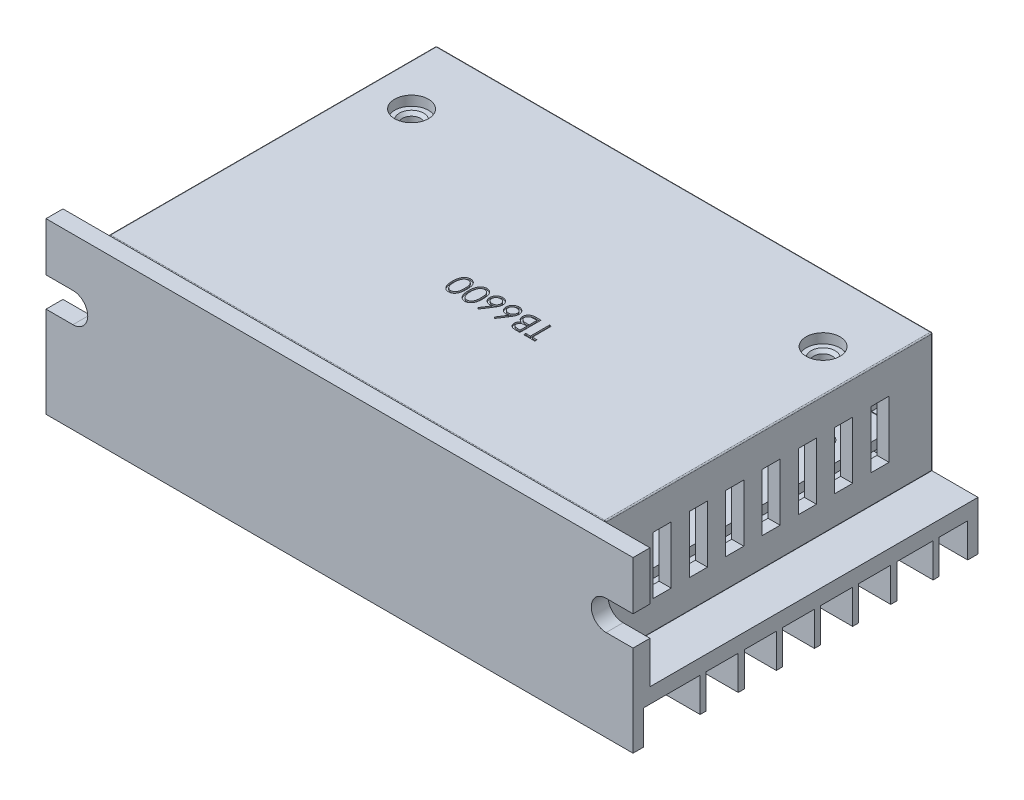
SolidWorks part; units mm, degrees
ref_plane "Front Plane" through (0, 0, 0) normal (0, 0, 1) x (1, 0, 0)
ref_plane "Top Plane" through (0, 0, 0) normal (0, 1, 0) x (1, 0, 0)
ref_plane "Right Plane" through (0, 0, 0) normal (1, 0, 0) x (0, 0, -1)
sketch "Sketch1" plane through (0, 0, 0) normal (1, 0, 0) x (0, 0, -1)
  line L1 (-28.5, 14) -> (28.5, 14)
  line L2 (-28.5, 14) -> (-28.5, -14)
  line L3 (-28.5, -14) -> (28.5, -14)
  line L4 (28.5, 14) -> (28.5, -14)
  line L5 (-28.5, 14) -> (28.5, -14) construction
  line L6 (-28.5, -14) -> (28.5, 14) construction
  point P0 (0, 0)
  dimension "D1" = 28
  dimension "D2" = 57
extrude "Base and Heat Sink" add sketch "Sketch1" along normal mid plane 97
sketch "Sketch2" plane through (0, 0, 0) normal (1, 0, 0) x (0, 0, -1)
  line L0 (28.5, 14) -> (-28.5, 14) construction
  line L1 (-25.7, 14) -> (28.5, 14)
  line L2 (-25.7, 14) -> (-25.7, -5.88)
  line L3 (-25.7, -5.88) -> (28.5, -5.88)
  line L4 (28.5, 14) -> (28.5, -5.88)
  line L5 (28.5, -14) -> (28.5, 14) construction
  line L6 (-28.5, 14) -> (-28.5, -14) construction
  line L7 (-28.5, -14) -> (28.5, -14) construction
  dimension "D1" = 2.8
  dimension "D2" = 8.12
extrude "Cut-Extrude1" cut sketch "Sketch2" against normal through all both and the other way through all
sketch "Sketch3" plane through (0, 0, 0) normal (1, 0, 0) x (0, 0, -1)
  line L0 (-28.5, -14) -> (28.5, -14) construction
  line L1 (-26.8, -14) -> (-17.42, -14)
  line L2 (-26.8, -14) -> (-26.8, -8.38)
  line L3 (-26.8, -8.38) -> (-17.42, -8.38)
  line L4 (-17.42, -14) -> (-17.42, -8.38)
  line L5 (-28.5, 14) -> (-28.5, -14) construction
  line L6 (-25.7, -5.88) -> (28.5, -5.88) construction
  line L7 (-10.12, -14) -> (-10.12, -8.38)
  line L8 (-16.42, -14) -> (-11.12, -14)
  line L9 (-16.42, -14) -> (-16.42, -8.38)
  line L10 (-16.42, -8.38) -> (-11.12, -8.38)
  line L11 (-11.12, -14) -> (-11.12, -8.38)
  line L12 (-10.12, -14) -> (-4.82, -14)
  line L13 (-4.82, -14) -> (-4.82, -8.38)
  line L14 (-3.82, -14) -> (-3.82, -8.38)
  line L15 (-3.82, -14) -> (1.48, -14)
  line L16 (1.48, -14) -> (1.48, -8.38)
  line L17 (2.48, -14) -> (2.48, -8.38)
  line L18 (2.48, -14) -> (7.78, -14)
  line L19 (7.78, -14) -> (7.78, -8.38)
  line L20 (8.78, -14) -> (8.78, -8.38)
  line L21 (8.78, -14) -> (14.08, -14)
  line L22 (14.08, -14) -> (14.08, -8.38)
  line L23 (28.5, -14) -> (28.5, -5.88) construction
  line L24 (15.08, -14) -> (21.08, -14)
  line L25 (15.08, -14) -> (15.08, -8.38)
  line L26 (15.08, -8.38) -> (21.08, -8.38)
  line L27 (21.08, -14) -> (21.08, -8.38)
  line L28 (22.08, -14) -> (26.8, -14)
  line L29 (22.08, -14) -> (22.08, -8.38)
  line L30 (22.08, -8.38) -> (26.8, -8.38)
  line L31 (26.8, -14) -> (26.8, -8.38)
  line L32 (-10.12, -8.38) -> (-4.82, -8.38)
  line L33 (-3.82, -8.38) -> (1.48, -8.38)
  line L34 (2.48, -8.38) -> (7.78, -8.38)
  line L35 (8.78, -8.38) -> (14.08, -8.38)
  dimension "D1" = 1.7
  dimension "D2" = 9.38
  dimension "D3" = 2.5
  dimension "D4" = 1
  dimension "D5" = 5.3
  dimension "D7" = 1
  dimension "D8" = 1
  dimension "D9" = 1
  dimension "D10" = 6
  dimension "D11" = 1
  dimension "D12" = 1.7
  dimension "D6" = 5
extrude "Cut-Extrude2" cut sketch "Sketch3" against normal through all both and the other way through all
sketch "Sketch4" plane through (0, -5.88, 0) normal (0, 1, 0) x (1, 0, 0)
  line L2 (-34, -20.8) -> (34, -20.8) construction
  line L3 (-34, -20.8) -> (-34, 17.4) construction
  line L4 (-34, 17.4) -> (34, 17.4) construction
  line L5 (34, -20.8) -> (34, 17.4) construction
  line L6 (-34, -20.8) -> (34, 17.4) construction
  line L7 (-34, 17.4) -> (34, -20.8) construction
  line L8 (-48.5, 28.5) -> (48.5, 28.5) construction
  circle A0 centre (-34, 17.4) radius 1.5
  circle A1 centre (34, 17.4) radius 1.5
  circle A2 centre (34, -20.8) radius 1.5
  circle A3 centre (-34, -20.8) radius 1.5
  point P0 (0, -1.7)
  dimension "D4" = 3
  dimension "D1" = 68
  dimension "D2" = 11.1
  dimension "D3" = 38.2
extrude "Cut-Extrude3" cut sketch "Sketch4" against normal blind 3
sketch "Sketch5" plane through (0, 0, 28.5) normal (0, 0, 1) x (1, 0, 0)
  line L0 (-48.5, 3.5) -> (52.8108, 3.5) construction
  line L1 (-48.5, 14) -> (-48.5, -14) construction
  line L2 (48.5, 14) -> (-48.5, 14) construction
  line L3 (48.5, 14) -> (48.5, -14) construction
  line L4 (41.6, 6.1377) -> (41.6, 0) construction
  line L5 (44.05, 1.05) -> (48.5, 1.05)
  line L6 (44.05, 5.95) -> (48.5, 5.95)
  line L7 (-41.6, 1.05) -> (-41.6, 6.49) construction
  line L8 (-44.05, 5.95) -> (-48.5, 5.95)
  line L9 (-44.05, 1.05) -> (-48.5, 1.05)
  line L10 (-48.5, 1.05) -> (-48.5, 5.95)
  line L11 (48.5, 1.05) -> (48.5, 5.95)
  arc A0 (44.05, 5.95) -> (44.05, 1.05) centre (44.05, 3.5) ccw
  arc A1 (-44.05, 1.05) -> (-44.05, 5.95) centre (-44.05, 3.5) ccw
  dimension "D2" = 4.9
  dimension "D4" = 6.9
  dimension "D1" = 10.5
  dimension "D3" = 4.45
extrude "Cut-Extrude4" cut sketch "Sketch5" against normal blind 3
sketch "Sketch6" plane through (0, 0, 0) normal (1, 0, 0) x (0, 0, -1)
  line L0 (-25.7, 14) -> (-25.7, 5.95) construction
  line L1 (-25.7, 14) -> (28.5, 14)
  line L2 (-25.7, 14) -> (-25.7, -5.88)
  line L3 (-25.7, -5.88) -> (28.5, -5.88)
  line L4 (28.5, 14) -> (28.5, -5.88)
  line L5 (-25.7, 14) -> (-28.5, 14) construction
extrude "Plastic Casing" add sketch "Sketch6" along normal mid plane 82 separate body
shell "Shell1" thickness 2 removed face at (0, 4.06, 25.7) removed face at (0, -5.88, -1.4)
fillet "Fillet1" radius 0.2 11 edges at (-41, -5.88, -1.4) (-41, 4.06, 25.7) (0, 14, 25.7) (-41, 14, -1.4) (0, -5.88, -28.5) (0, 14, -28.5) (-41, 4.06, -28.5) (41, 14, -1.4) (41, 4.06, -28.5) (41, -5.88, -1.4) (41, 4.06, 25.7)
sketch "Sketch9" plane through (0, 14, 0) normal (0, 1, 0) x (1, 0, 0)
  circle A0 centre (-34, 17.4) radius 1.5 construction
  circle A1 centre (34, 17.4) radius 1.5 construction
  circle A2 centre (-34, 17.4) radius 1.5
  circle A3 centre (34, 17.4) radius 1.5
sketch "Sketch10" plane through (0, 12, 0) normal (0, -1, 0) x (1, 0, 0)
  circle A0 centre (34, -17.4) radius 3.975
  circle A1 centre (-34, -17.4) radius 3.975
  dimension "D1" = 7.95
extrude "Boss-Extrude3" add sketch "Sketch10" along normal blind 1.2
sketch "Sketch11" plane through (0, 10.8, 0) normal (0, -1, 0) x (1, 0, 0)
  circle A0 centre (-34, -17.4) radius 1.5 construction
  circle A1 centre (34, -17.4) radius 1.5 construction
  circle A2 centre (-34, -17.4) radius 1.5
  circle A3 centre (34, -17.4) radius 1.5
extrude "Cut-Extrude5" cut sketch "Sketch11" against normal blind 11.2
sketch "Sketch12" plane through (0, 14, 0) normal (0, 1, 0) x (1, 0, 0)
  circle A0 centre (-34, 17.4) radius 2.8
  circle A1 centre (34, 17.4) radius 2.8
  dimension "D1" = 5.6
extrude "Cut-Extrude6" cut sketch "Sketch12" against normal blind 1.6
chamfer "Chamfer1" distance 0.5 angle 45 2 edges at (34, 12.4, -15.9) (-34, 12.4, -15.9)
sketch "Sketch13" plane through (0, 0, -28.5) normal (0, 0, -1) x (-1, 0, 0)
  line L0 (41, 13.8) -> (41, -5.68) construction
  line L1 (-33.9, -0.38) -> (32.5, -0.38)
  line L2 (-33.9, -0.38) -> (-33.9, 10.25)
  line L3 (-33.9, 10.25) -> (32.5, 10.25)
  line L4 (32.5, -0.38) -> (32.5, 10.25)
  line L5 (-41, -5.68) -> (-41, 13.8) construction
  line L6 (-40.8, 14) -> (40.8, 14) construction
  line L7 (40.8, -5.88) -> (-40.8, -5.88) construction
  dimension "D1" = 8.5
  dimension "D2" = 7.1
  dimension "D3" = 3.75
  dimension "D4" = 5.5
extrude "Cut-Extrude7" cut sketch "Sketch13" against normal up to surface (2 mm away) up to face at (0, 3.06, -26.5)
sketch "Sketch14" plane through (0, 0, 0) normal (1, 0, 0) x (0, 0, -1)
  line L0 (28.5, -5.68) -> (28.5, 13.8) construction
  line L1 (21.3, 8.45) -> (18.3, 8.45)
  line L2 (21.3, 8.45) -> (21.3, -1.0244)
  line L3 (21.3, -1.0244) -> (18.3, -1.0244)
  line L4 (18.3, 8.45) -> (18.3, -1.0244)
  line L5 (28.3, 14) -> (-25.5, 14) construction
  line L7 (15.3, 8.45) -> (12.3, 8.45)
  line L8 (15.3, 8.45) -> (15.3, -1.0244)
  line L9 (15.3, -1.0244) -> (12.3, -1.0244)
  line L10 (12.3, 8.45) -> (12.3, -1.0244)
  line L11 (9.3, 8.45) -> (6.3, 8.45)
  line L12 (9.3, 8.45) -> (9.3, -1.0244)
  line L13 (9.3, -1.0244) -> (6.3, -1.0244)
  line L14 (6.3, 8.45) -> (6.3, -1.0244)
  line L15 (3.3, 8.45) -> (0.3, 8.45)
  line L16 (3.3, 8.45) -> (3.3, -1.0244)
  line L17 (3.3, -1.0244) -> (0.3, -1.0244)
  line L18 (0.3, 8.45) -> (0.3, -1.0244)
  line L19 (-2.7, 8.45) -> (-5.7, 8.45)
  line L20 (-2.7, 8.45) -> (-2.7, -1.0244)
  line L21 (-2.7, -1.0244) -> (-5.7, -1.0244)
  line L22 (-5.7, 8.45) -> (-5.7, -1.0244)
  line L23 (-8.7, 8.45) -> (-11.7, 8.45)
  line L24 (-8.7, 8.45) -> (-8.7, -1.0244)
  line L25 (-8.7, -1.0244) -> (-11.7, -1.0244)
  line L26 (-11.7, 8.45) -> (-11.7, -1.0244)
  line L27 (-14.7, 8.45) -> (-17.7, 8.45)
  line L28 (-14.7, 8.45) -> (-14.7, -1.0244)
  line L29 (-14.7, -1.0244) -> (-17.7, -1.0244)
  line L30 (-17.7, 8.45) -> (-17.7, -1.0244)
  dimension "D1" = 7.2
  dimension "D2" = 3
  dimension "D3" = 5.55
  dimension "D4" = 7
extrude "Cut-Extrude9" cut sketch "Sketch14" along normal up to surface (41 mm away) up to face at (41, 4.06, -1.4)
sketch "Sketch15" plane through (-41, 0, 0) normal (-1, 0, 0) x (0, 0, 1)
  line L0 (14.7, 8.45) -> (14.7, -1.0244) construction
  line L1 (17.7, 8.45) -> (14.7, 8.45) construction
  line L2 (17.7, -1.0244) -> (17.7, 8.45) construction
  line L3 (14.7, -1.0244) -> (17.7, -1.0244) construction
  line L4 (8.7, -1.0244) -> (11.7, -1.0244) construction
  line L5 (8.7, 8.45) -> (8.7, -1.0244) construction
  line L6 (11.7, 8.45) -> (8.7, 8.45) construction
  line L7 (11.7, -1.0244) -> (11.7, 8.45) construction
  line L8 (-21.3, -1.0244) -> (-18.3, -1.0244) construction
  line L9 (-21.3, 8.45) -> (-21.3, -1.0244) construction
  line L10 (-18.3, 8.45) -> (-21.3, 8.45) construction
  line L11 (-18.3, -1.0244) -> (-18.3, 8.45) construction
  line L12 (14.7, 8.45) -> (14.7, -1.0244)
  line L13 (17.7, 8.45) -> (14.7, 8.45)
  line L14 (17.7, -1.0244) -> (17.7, 8.45)
  line L15 (14.7, -1.0244) -> (17.7, -1.0244)
  line L16 (8.7, -1.0244) -> (11.7, -1.0244)
  line L17 (8.7, 8.45) -> (8.7, -1.0244)
  line L18 (11.7, 8.45) -> (8.7, 8.45)
  line L19 (11.7, -1.0244) -> (11.7, 8.45)
  line L20 (-21.3, -1.0244) -> (-18.3, -1.0244)
  line L21 (-21.3, 8.45) -> (-21.3, -1.0244)
  line L22 (-18.3, 8.45) -> (-21.3, 8.45)
  line L23 (-18.3, -1.0244) -> (-18.3, 8.45)
extrude "Cut-Extrude10" cut sketch "Sketch15" against normal up to surface (2 mm away) up to face at (-39, 3.06, -0.4)
sketch "Sketch16" plane through (-41, 0, 0) normal (-1, 0, 0) x (0, 0, 1)
  line L0 (25.7, -5.88) -> (-28.3, -5.88) construction
  line L1 (-15.1674, 10.82) -> (3.6826, 10.82)
  line L2 (-15.1674, 10.82) -> (-15.1674, 0.62)
  line L3 (-15.1674, 0.62) -> (3.6826, 0.62)
  line L4 (3.6826, 10.82) -> (3.6826, 0.62)
  dimension "D1" = 18.85
  dimension "D2" = 10.2
  dimension "D3" = 6.5
extrude "Cut-Extrude11" cut sketch "Sketch16" against normal up to surface (2 mm away) up to face at (-39, 3.7128, 10.2)
ref_plane "Plane1" through (0, -0.88, 0) normal (0, 1, 0) x (1, 0, 0)
sketch "Sketch17" plane through (0, -0.88, 0) normal (0, 1, 0) x (1, 0, 0)
  line L0 (-48.5, -25.7) -> (48.5, -25.7) construction
  line L1 (38.275, -24.7) -> (-38.275, -24.7)
  line L2 (38.275, -24.7) -> (38.275, 25.4)
  line L3 (38.275, 25.4) -> (-38.275, 25.4)
  line L4 (-38.275, -24.7) -> (-38.275, 25.4)
  circle A0 centre (-34, -20.8) radius 1.5 construction
  circle A1 centre (-34, 17.4) radius 1.5 construction
  circle A2 centre (34, 17.4) radius 1.5 construction
  circle A3 centre (34, -20.8) radius 1.5 construction
  circle A4 centre (-34, -20.8) radius 1.5
  circle A5 centre (-34, 17.4) radius 1.5
  circle A6 centre (34, 17.4) radius 1.5
  circle A7 centre (34, -20.8) radius 1.5
  point P18 (0, -24.7)
  dimension "D1" = 50.1
  dimension "D2" = 1
  dimension "D3" = 76.55
extrude "Boss-Extrude4" add sketch "Sketch17" along normal blind 1.5 separate body
ref_plane "Plane2" through (0, 0, -33.5) normal (0, 0, -1) x (-1, 0, 0)
sketch "Sketch18" plane through (0, 0, -33.5) normal (0, 0, -1) x (-1, 0, 0)
  line L0 (-38.275, 0.62) -> (38.275, 0.62) construction
  line L1 (-33.9, 0.62) -> (27.4, 0.62)
  line L2 (-33.9, 0.62) -> (-33.9, 8.62)
  line L3 (-33.9, 8.62) -> (27.4, 8.62)
  line L4 (27.4, 0.62) -> (27.4, 8.62)
  line L5 (-33.9, 10.25) -> (-33.9, -0.38) construction
  dimension "D1" = 8
  dimension "D2" = 61.3
extrude "Connector" add sketch "Sketch18" against normal blind 12 separate body
sketch "Sketch19" plane through (0, 0, -33.5) normal (0, 0, -1) x (-1, 0, 0)
  line L0 (-3.3029, 9.6458) -> (-3.3029, -7.8401) construction
  line L1 (-33.9, 7.1295) -> (-33.9, 1.6983) construction
  line L2 (-33.9, 8.62) -> (-33.9, 0.62) construction
  line L3 (-28.7917, 7.1867) -> (-28.7917, 1.7555) construction
  line L4 (-23.6833, 7.2439) -> (-23.6833, 1.8127) construction
  line L5 (-18.575, 7.3012) -> (-18.575, 1.8699) construction
  line L6 (-13.4667, 7.3584) -> (-13.4667, 1.9272) construction
  line L7 (-8.3583, 7.4156) -> (-8.3583, 1.9844) construction
  line L8 (-3.25, 7.4728) -> (-3.25, 2.0416) construction
  line L9 (1.8583, 7.53) -> (1.8583, 2.0988) construction
  line L10 (6.9667, 7.5873) -> (6.9667, 2.1561) construction
  line L11 (12.075, 7.6445) -> (12.075, 2.2133) construction
  line L12 (17.1833, 7.7017) -> (17.1833, 2.2705) construction
  line L13 (22.2917, 7.7589) -> (22.2917, 2.3277) construction
  line L14 (27.4, 7.8162) -> (27.4, 2.385) construction
  line L15 (-33.9, 7.1295) -> (-28.7917, 7.1867) construction
  dimension "D2" = 5.1087
  dimension "D1" = 13
sketch "Sketch20" plane through (0, 0, -33.5) normal (0, 0, -1) x (-1, 0, 0)
  line L0 (-33.9, 8.62) -> (-33.9, 0.62) construction
  line L1 (-33.9, 7.02) -> (27.4, 7.02)
  line L2 (-33.9, 7.02) -> (-33.9, 1.62)
  line L3 (-33.9, 1.62) -> (-33.3515, 1.62)
  line L4 (27.4, 7.02) -> (27.4, 1.62)
  line L5 (27.4, 0.62) -> (27.4, 8.62) construction
  line L6 (27.4, 8.62) -> (-33.9, 8.62) construction
  line L7 (-31.3458, 16.2754) -> (-31.3458, 1.62) construction
  line L8 (-28.7917, 7.1867) -> (-28.7917, 1.7555) construction
  line L9 (-29.3401, 1.62) -> (-28.2394, 1.62)
  line L10 (24.8458, 7.7121) -> (24.8458, 1.62) construction
  line L11 (22.2917, 7.7589) -> (22.2917, 2.3277) construction
  line L12 (-33.3515, 1.62) -> (-28.2402, 1.6208) construction
  line L13 (-24.2297, 1.62) -> (-23.1272, 1.62)
  line L14 (-19.1193, 1.62) -> (-18.0151, 1.62)
  line L15 (-14.0089, 1.62) -> (-12.9029, 1.62)
  line L16 (-8.8985, 1.62) -> (-7.7907, 1.62)
  line L17 (-3.7881, 1.62) -> (-2.6786, 1.62)
  line L18 (1.3223, 1.62) -> (2.4336, 1.62)
  line L19 (6.4327, 1.62) -> (7.5458, 1.62)
  line L20 (11.5432, 1.62) -> (12.6579, 1.62)
  line L21 (16.6536, 1.62) -> (17.7701, 1.62)
  line L22 (21.764, 1.62) -> (22.8823, 1.62)
  line L23 (26.8744, 1.62) -> (27.4, 1.62)
  arc A0 (-33.3515, 1.62) -> (-29.3401, 1.62) centre (-31.3458, 3.7715) ccw
  arc A1 (-28.2394, 1.62) -> (-24.2297, 1.62) centre (-26.2345, 3.7723) ccw
  arc A2 (-23.1272, 1.62) -> (-19.1193, 1.62) centre (-21.1233, 3.7731) ccw
  arc A3 (-18.0151, 1.62) -> (-14.0089, 1.62) centre (-16.012, 3.7739) ccw
  arc A4 (-12.9029, 1.62) -> (-8.8985, 1.62) centre (-10.9007, 3.7748) ccw
  arc A5 (-7.7907, 1.62) -> (-3.7881, 1.62) centre (-5.7894, 3.7756) ccw
  arc A6 (-2.6786, 1.62) -> (1.3223, 1.62) centre (-0.6781, 3.7764) ccw
  arc A7 (2.4336, 1.62) -> (6.4327, 1.62) centre (4.4332, 3.7772) ccw
  arc A8 (7.5458, 1.62) -> (11.5432, 1.62) centre (9.5445, 3.778) ccw
  arc A9 (12.6579, 1.62) -> (16.6536, 1.62) centre (14.6557, 3.7788) ccw
  arc A10 (17.7701, 1.62) -> (21.764, 1.62) centre (19.767, 3.7796) ccw
  arc A11 (22.8823, 1.62) -> (26.8744, 1.62) centre (24.8783, 3.7804) ccw
  dimension "D5" = 2.9414
  dimension "D1" = 5.4
  dimension "D2" = 1.6
  dimension "D4" = 5.1113
  dimension "D3" = 12
extrude "Cut-Extrude12" cut sketch "Sketch20" against normal blind 10.5
sketch "Sketch21" plane through (0, 0, -23) normal (0, 0, -1) x (-1, 0, 0)
  line L0 (-31.3458, 6.0298) -> (-31.3458, 2.1596) construction
  line L1 (-33.9, 7.1295) -> (-33.9, 1.6983) construction
  line L2 (-28.7917, 7.1867) -> (-28.7917, 1.7555) construction
  line L3 (-31.3458, 4.0947) -> (24.8458, 4.0947) construction
  line L4 (24.8458, 6.0298) -> (24.8458, 2.1596) construction
  line L5 (22.2917, 7.7589) -> (22.2917, 2.3277) construction
  line L6 (27.4, 7.8162) -> (27.4, 2.385) construction
  line L7 (-26.4875, 4.3447) -> (-25.9875, 4.3447)
  line L8 (-31.5958, 4.3447) -> (-31.0958, 4.3447)
  line L9 (-31.5958, 4.3447) -> (-31.5958, 3.8447)
  line L10 (-31.5958, 3.8447) -> (-31.0958, 3.8447)
  line L11 (-31.0958, 4.3447) -> (-31.0958, 3.8447)
  line L12 (-31.5958, 4.3447) -> (-31.0958, 3.8447) construction
  line L13 (-31.5958, 3.8447) -> (-31.0958, 4.3447) construction
  line L14 (-26.4875, 4.3447) -> (-26.4875, 3.8447)
  line L15 (-26.4875, 3.8447) -> (-25.9875, 3.8447)
  line L16 (-25.9875, 4.3447) -> (-25.9875, 3.8447)
  line L17 (-26.4875, 4.3447) -> (-25.9875, 3.8447) construction
  line L18 (-26.4875, 3.8447) -> (-25.9875, 4.3447) construction
  line L19 (-21.3792, 4.3447) -> (-20.8792, 4.3447)
  line L20 (-21.3792, 4.3447) -> (-21.3792, 3.8447)
  line L21 (-21.3792, 3.8447) -> (-20.8792, 3.8447)
  line L22 (-20.8792, 4.3447) -> (-20.8792, 3.8447)
  line L23 (-21.3792, 4.3447) -> (-20.8792, 3.8447) construction
  line L24 (-21.3792, 3.8447) -> (-20.8792, 4.3447) construction
  line L25 (-16.2708, 4.3447) -> (-15.7708, 4.3447)
  line L26 (-16.2708, 4.3447) -> (-16.2708, 3.8447)
  line L27 (-16.2708, 3.8447) -> (-15.7708, 3.8447)
  line L28 (-15.7708, 4.3447) -> (-15.7708, 3.8447)
  line L29 (-16.2708, 4.3447) -> (-15.7708, 3.8447) construction
  line L30 (-16.2708, 3.8447) -> (-15.7708, 4.3447) construction
  line L31 (-11.1625, 4.3447) -> (-10.6625, 4.3447)
  line L32 (-11.1625, 4.3447) -> (-11.1625, 3.8447)
  line L33 (-11.1625, 3.8447) -> (-10.6625, 3.8447)
  line L34 (-10.6625, 4.3447) -> (-10.6625, 3.8447)
  line L35 (-11.1625, 4.3447) -> (-10.6625, 3.8447) construction
  line L36 (-11.1625, 3.8447) -> (-10.6625, 4.3447) construction
  line L37 (-6.0542, 4.3447) -> (-5.5542, 4.3447)
  line L38 (-6.0542, 4.3447) -> (-6.0542, 3.8447)
  line L39 (-6.0542, 3.8447) -> (-5.5542, 3.8447)
  line L40 (-5.5542, 4.3447) -> (-5.5542, 3.8447)
  line L41 (-6.0542, 4.3447) -> (-5.5542, 3.8447) construction
  line L42 (-6.0542, 3.8447) -> (-5.5542, 4.3447) construction
  line L43 (-0.9458, 4.3447) -> (-0.4458, 4.3447)
  line L44 (-0.9458, 4.3447) -> (-0.9458, 3.8447)
  line L45 (-0.9458, 3.8447) -> (-0.4458, 3.8447)
  line L46 (-0.4458, 4.3447) -> (-0.4458, 3.8447)
  line L47 (-0.9458, 4.3447) -> (-0.4458, 3.8447) construction
  line L48 (-0.9458, 3.8447) -> (-0.4458, 4.3447) construction
  line L49 (4.1625, 4.3447) -> (4.6625, 4.3447)
  line L50 (4.1625, 4.3447) -> (4.1625, 3.8447)
  line L51 (4.1625, 3.8447) -> (4.6625, 3.8447)
  line L52 (4.6625, 4.3447) -> (4.6625, 3.8447)
  line L53 (4.1625, 4.3447) -> (4.6625, 3.8447) construction
  line L54 (4.1625, 3.8447) -> (4.6625, 4.3447) construction
  line L55 (9.2708, 4.3447) -> (9.7708, 4.3447)
  line L56 (9.2708, 4.3447) -> (9.2708, 3.8447)
  line L57 (9.2708, 3.8447) -> (9.7708, 3.8447)
  line L58 (9.7708, 4.3447) -> (9.7708, 3.8447)
  line L59 (9.2708, 4.3447) -> (9.7708, 3.8447) construction
  line L60 (9.2708, 3.8447) -> (9.7708, 4.3447) construction
  line L61 (14.3792, 4.3447) -> (14.8792, 4.3447)
  line L62 (14.3792, 4.3447) -> (14.3792, 3.8447)
  line L63 (14.3792, 3.8447) -> (14.8792, 3.8447)
  line L64 (14.8792, 4.3447) -> (14.8792, 3.8447)
  line L65 (14.3792, 4.3447) -> (14.8792, 3.8447) construction
  line L66 (14.3792, 3.8447) -> (14.8792, 4.3447) construction
  line L67 (19.4875, 4.3447) -> (19.9875, 4.3447)
  line L68 (19.4875, 4.3447) -> (19.4875, 3.8447)
  line L69 (19.4875, 3.8447) -> (19.9875, 3.8447)
  line L70 (19.9875, 4.3447) -> (19.9875, 3.8447)
  line L71 (19.4875, 4.3447) -> (19.9875, 3.8447) construction
  line L72 (19.4875, 3.8447) -> (19.9875, 4.3447) construction
  line L73 (24.5958, 4.3447) -> (25.0958, 4.3447)
  line L74 (24.5958, 4.3447) -> (24.5958, 3.8447)
  line L75 (24.5958, 3.8447) -> (25.0958, 3.8447)
  line L76 (25.0958, 4.3447) -> (25.0958, 3.8447)
  line L77 (24.5958, 4.3447) -> (25.0958, 3.8447) construction
  line L78 (24.5958, 3.8447) -> (25.0958, 4.3447) construction
  line L79 (-31.5958, 4.3447) -> (-26.4875, 4.3447) construction
  dimension "D1" = 0.5
  dimension "D2" = 0.5
  dimension "D4" = 5.1083
  dimension "D3" = 12
extrude "Boss-Extrude6" add sketch "Sketch21" along normal blind 10.5
chamfer "Chamfer2" distance 0.6 angle 15 48 edges at (-24.8458, 3.8447, -33.5) (-24.5958, 4.0947, -33.5) (-24.8458, 4.3447, -33.5) (-25.0958, 4.0947, -33.5) (-19.7375, 3.8447, -33.5) (-19.4875, 4.0947, -33.5) (-19.7375, 4.3447, -33.5) (-19.9875, 4.0947, -33.5) (-14.6292, 3.8447, -33.5) (-14.3792, 4.0947, -33.5) (-14.6292, 4.3447, -33.5) (-14.8792, 4.0947, -33.5) (-9.5208, 3.8447, -33.5) (-9.2708, 4.0947, -33.5) (-9.5208, 4.3447, -33.5) (-9.7708, 4.0947, -33.5) (-4.4125, 3.8447, -33.5) (-4.1625, 4.0947, -33.5) (-4.4125, 4.3447, -33.5) (-4.6625, 4.0947, -33.5) (0.6958, 3.8447, -33.5) (0.9458, 4.0947, -33.5) (0.6958, 4.3447, -33.5) (0.4458, 4.0947, -33.5) (5.8042, 3.8447, -33.5) (6.0542, 4.0947, -33.5) (5.8042, 4.3447, -33.5) (5.5542, 4.0947, -33.5) (10.9125, 3.8447, -33.5) (11.1625, 4.0947, -33.5) (10.9125, 4.3447, -33.5) (10.6625, 4.0947, -33.5) (16.0208, 3.8447, -33.5) (16.2708, 4.0947, -33.5) (16.0208, 4.3447, -33.5) (15.7708, 4.0947, -33.5) (21.1292, 3.8447, -33.5) (21.3792, 4.0947, -33.5) (21.1292, 4.3447, -33.5) (20.8792, 4.0947, -33.5) (26.2375, 3.8447, -33.5) (26.4875, 4.0947, -33.5) (26.2375, 4.3447, -33.5) (25.9875, 4.0947, -33.5) (31.3458, 3.8447, -33.5) (31.5958, 4.0947, -33.5) (31.3458, 4.3447, -33.5) (31.0958, 4.0947, -33.5) first distance on face at (-24.8458, 3.8447, -28.25) first distance on face at (-24.5958, 4.0947, -28.25) first distance on face at (-24.8458, 4.3447, -28.25) first distance on face at (-25.0958, 4.0947, -28.25) first distance on face at (-19.7375, 3.8447, -28.25) first distance on face at (-19.4875, 4.0947, -28.25) first distance on face at (-19.7375, 4.3447, -28.25) first distance on face at (-19.9875, 4.0947, -28.25) first distance on face at (-14.6292, 3.8447, -28.25) first distance on face at (-14.3792, 4.0947, -28.25) first distance on face at (-14.6292, 4.3447, -28.25) first distance on face at (-14.8792, 4.0947, -28.25) first distance on face at (-9.5208, 3.8447, -28.25) first distance on face at (-9.2708, 4.0947, -28.25) first distance on face at (-9.5208, 4.3447, -28.25) first distance on face at (-9.7708, 4.0947, -28.25) first distance on face at (-4.4125, 3.8447, -28.25) first distance on face at (-4.1625, 4.0947, -28.25) first distance on face at (-4.4125, 4.3447, -28.25) first distance on face at (-4.6625, 4.0947, -28.25) first distance on face at (0.6958, 3.8447, -28.25) first distance on face at (0.9458, 4.0947, -28.25) first distance on face at (0.6958, 4.3447, -28.25) first distance on face at (0.4458, 4.0947, -28.25) first distance on face at (5.8042, 3.8447, -28.25) first distance on face at (6.0542, 4.0947, -28.25) first distance on face at (5.8042, 4.3447, -28.25) first distance on face at (5.5542, 4.0947, -28.25) first distance on face at (10.9125, 3.8447, -28.25) first distance on face at (11.1625, 4.0947, -28.25) first distance on face at (10.9125, 4.3447, -28.25) first distance on face at (10.6625, 4.0947, -28.25) first distance on face at (16.0208, 3.8447, -28.25) first distance on face at (16.2708, 4.0947, -28.25) first distance on face at (16.0208, 4.3447, -28.25) first distance on face at (15.7708, 4.0947, -28.25) first distance on face at (21.1292, 3.8447, -28.25) first distance on face at (21.3792, 4.0947, -28.25) first distance on face at (21.1292, 4.3447, -28.25) first distance on face at (20.8792, 4.0947, -28.25) first distance on face at (26.2375, 3.8447, -28.25) first distance on face at (26.4875, 4.0947, -28.25) first distance on face at (26.2375, 4.3447, -28.25) first distance on face at (25.9875, 4.0947, -28.25) first distance on face at (31.3458, 3.8447, -28.25) first distance on face at (31.5958, 4.0947, -28.25) first distance on face at (31.3458, 4.3447, -28.25) first distance on face at (31.0958, 4.0947, -28.25)
ref_plane "Lights" through (0, 0, -29.5) normal (0, 0, -1) x (-1, 0, 0)
sketch "Sketch22" plane through (0, 0, -29.5) normal (0, 0, -1) x (-1, 0, 0)
  line L0 (27.4, 0.62) -> (27.4, 8.62) construction
  line L1 (27.4, 0.62) -> (32.5, 0.62)
  line L2 (27.4, 0.62) -> (27.4, 10.25)
  line L3 (27.4, 10.25) -> (32.5, 10.25)
  line L4 (32.5, 0.62) -> (32.5, 10.25)
  line L5 (-38.275, 0.62) -> (38.275, 0.62) construction
extrude "Boss-Extrude7" add sketch "Sketch22" against normal blind 9 separate body
sketch "Sketch23" plane through (0, 0, -29.5) normal (0, 0, -1) x (-1, 0, 0)
  line L0 (29.95, 10.25) -> (29.95, 0.62) construction
  line L1 (32.5, 10.25) -> (27.4, 10.25) construction
  line L2 (27.4, 0.62) -> (32.5, 0.62) construction
  circle A0 centre (29.95, 7.04) radius 1
  dimension "D2" = 2
  dimension "D4" = 3.21
extrude "Boss-Extrude8" add sketch "Sketch23" along normal blind 4 separate body
sketch "Sketch24" plane through (0, 0, -33.5) normal (0, 0, -1) x (-1, 0, 0)
  line L0 (29.95, 8.2458) -> (29.95, 5.8056) construction
ref_plane "Plane4" through (-29.95, 0, 0) normal (-1, 0, 0) x (0, 0, 1)
sketch "Sketch26" plane through (-29.95, 0, 0) normal (-1, 0, 0) x (0, 0, 1)
  line L0 (-33.8971, 7.04) -> (-31.2542, 7.04) construction
  line L3 (-33.5, 6.04) -> (-32.3126, 6.04) construction
  line L6 (-33.5, 8.04) -> (-33.5, 6.04) construction
  line L7 (-33.5, 8.04) -> (-32.6838, 8.04) construction
  line L8 (-29.5, 10.714) -> (-29.5, -10.714) construction
  line L9 (-33, 7.04) -> (-33.7369, 7.04)
  line L10 (-33.7369, 7.04) -> (-33.7369, 6.04)
  line L11 (-33.7369, 6.04) -> (-32, 6.04)
  arc A0 (-33, 7.04) -> (-32, 6.04) centre (-32, 7.04) ccw
  dimension "D2" = 2
  dimension "D1" = 1
  dimension "D3" = 2.5
revolve "Cut-Revolve2" cut sketch "Sketch26" angle 360 about L0
sketch "Sketch27" plane through (0, 0, -29.5) normal (0, 0, -1) x (-1, 0, 0)
  line L0 (29.95, 10.25) -> (29.95, 0.6198) construction
  line L1 (32.5, 10.25) -> (27.4, 10.25) construction
  line L2 (29.95, -5.2965) -> (29.95, 5.2965) construction
  line L3 (27.4, 0.62) -> (32.5, 0.62) construction
  circle A0 centre (29.95, 3.83) radius 1
  dimension "D1" = 2
  dimension "D2" = 3.21
extrude "Boss-Extrude9" add sketch "Sketch27" along normal blind 4 separate body
sketch "Sketch28" plane through (-29.95, 0, 0) normal (-1, 0, 0) x (0, 0, 1)
  line L0 (-33.7212, 3.83) -> (-29.3271, 3.83) construction
  line L1 (-29.5, 4.83) -> (-33.5, 4.83) construction
  line L2 (-33.5, 2.83) -> (-29.5, 2.83) construction
  line L3 (-32, 8.04) -> (-32, 6.04) construction
  line L4 (-32, 7.04) -> (-32, 2.3515) construction
  line L5 (-32, 2.83) -> (-33.7212, 2.83)
  line L6 (-33.7212, 2.83) -> (-33.7212, 3.83)
  line L7 (-33.7212, 3.83) -> (-33, 3.83)
  arc A0 (-33, 3.83) -> (-32, 2.83) centre (-32, 3.83) ccw
  dimension "D1" = 2
revolve "Cut-Revolve3" cut sketch "Sketch28" angle 360 about L0
sketch "Sketch29" plane through (0, 0.62, 0) normal (0, 1, 0) x (1, 0, 0)
  line L0 (-40.8, 5.7424) -> (-12.823, 5.7424) construction
  line L1 (-40.8, 28.3) -> (-40.8, -25.5) construction
  line L2 (-40, 15.1674) -> (-13.8921, 15.1674) construction
  line L3 (-39, 15.1674) -> (-41, 15.1674) construction
  line L4 (-39, -3.6826) -> (-13.8921, -3.6826) construction
  line L6 (-36.7603, 15.1674) -> (-26.3903, 15.1674)
  line L7 (-36.7603, 15.1674) -> (-36.7603, -3.6826)
  line L8 (-36.7603, -3.6826) -> (-26.3903, -3.6826)
  line L9 (-26.3903, 15.1674) -> (-26.3903, -3.6826)
  dimension "D1" = 9.425
  dimension "D2" = 10.37
extrude "Switch Holder" add sketch "Sketch29" along normal blind 10 separate body
sketch "Sketch30" plane through (-36.7603, 0, 0) normal (-1, 0, 0) x (0, 0, 1)
  line L0 (-15.1674, 10.62) -> (3.6826, 10.62) construction
  line L1 (-13.7174, 10.62) -> (-12.2674, 10.62)
  line L2 (-13.7174, 10.62) -> (-13.7174, 6.5757)
  line L3 (-13.7174, 6.5757) -> (-12.2674, 6.5757)
  line L4 (-12.2674, 10.62) -> (-12.2674, 6.5757)
  line L5 (-13.7174, 10.9969) -> (-13.7174, 4.3932) construction
  line L6 (2.6826, 10.9969) -> (2.6826, 4.3932) construction
  line L7 (3.6826, 10.62) -> (3.6826, 0.62) construction
  line L8 (-15.1674, 10.62) -> (-15.1674, 0.62) construction
  line L9 (-10.8174, 10.62) -> (-9.3674, 10.62)
  line L10 (-10.8174, 10.62) -> (-10.8174, 6.5757)
  line L11 (-10.8174, 6.5757) -> (-9.3674, 6.5757)
  line L12 (-9.3674, 10.62) -> (-9.3674, 6.5757)
  line L13 (-7.9174, 10.62) -> (-6.4674, 10.62)
  line L14 (-7.9174, 10.62) -> (-7.9174, 6.5757)
  line L15 (-7.9174, 6.5757) -> (-6.4674, 6.5757)
  line L16 (-6.4674, 10.62) -> (-6.4674, 6.5757)
  line L17 (-5.0174, 10.62) -> (-3.5674, 10.62)
  line L18 (-5.0174, 10.62) -> (-5.0174, 6.5757)
  line L19 (-5.0174, 6.5757) -> (-3.5674, 6.5757)
  line L20 (-3.5674, 10.62) -> (-3.5674, 6.5757)
  line L21 (-2.1174, 10.62) -> (-0.6674, 10.62)
  line L22 (-2.1174, 10.62) -> (-2.1174, 6.5757)
  line L23 (-2.1174, 6.5757) -> (-0.6674, 6.5757)
  line L24 (-0.6674, 10.62) -> (-0.6674, 6.5757)
  line L25 (0.7826, 10.62) -> (2.2326, 10.62)
  line L26 (0.7826, 10.62) -> (0.7826, 6.5757)
  line L27 (0.7826, 6.5757) -> (2.2326, 6.5757)
  line L28 (2.2326, 10.62) -> (2.2326, 6.5757)
  line L29 (-13.7174, 10.62) -> (-10.8174, 10.62) construction
  dimension "D1" = 1.45
  dimension "D2" = 1
  dimension "D3" = 1.45
  dimension "D4" = 6
  dimension "D5" = 2.9
extrude "Cut-Extrude13" cut sketch "Sketch30" against normal blind 1.5
chamfer "Chamfer3" distance 2 angle 45 1 edges at (-26.3903, 10.62, -5.7424)
sketch "Sketch31" plane through (0, 6.5757, 0) normal (0, 1, 0) x (1, 0, 0)
  line L0 (-35.2603, 12.2674) -> (-36.7603, 12.2674) construction
  line L1 (-35.2603, 13.7174) -> (-36.2603, 13.7174)
  line L2 (-35.2603, 13.7174) -> (-35.2603, 12.2674)
  line L3 (-35.2603, 12.2674) -> (-36.2603, 12.2674)
  line L4 (-36.2603, 13.7174) -> (-36.2603, 12.2674)
  line L5 (-35.2603, 9.3674) -> (-36.7603, 9.3674) construction
  line L6 (-35.2603, 10.8174) -> (-36.2603, 10.8174)
  line L7 (-35.2603, 10.8174) -> (-35.2603, 9.3674)
  line L8 (-35.2603, 9.3674) -> (-36.2603, 9.3674)
  line L9 (-36.2603, 10.8174) -> (-36.2603, 9.3674)
  line L10 (-35.2603, 6.4674) -> (-36.7603, 6.4674) construction
  line L11 (-35.2603, 7.9174) -> (-36.2603, 7.9174)
  line L12 (-35.2603, 7.9174) -> (-35.2603, 6.4674)
  line L13 (-35.2603, 6.4674) -> (-36.2603, 6.4674)
  line L14 (-36.2603, 7.9174) -> (-36.2603, 6.4674)
  line L15 (-35.2603, 3.5674) -> (-36.7603, 3.5674) construction
  line L16 (-35.2603, 5.0174) -> (-36.2603, 5.0174)
  line L17 (-35.2603, 5.0174) -> (-35.2603, 3.5674)
  line L18 (-35.2603, 3.5674) -> (-36.2603, 3.5674)
  line L19 (-36.2603, 5.0174) -> (-36.2603, 3.5674)
  line L20 (-35.2603, 0.6674) -> (-36.7603, 0.6674) construction
  line L21 (-35.2603, 2.1174) -> (-36.2603, 2.1174)
  line L22 (-35.2603, 2.1174) -> (-35.2603, 0.6674)
  line L23 (-35.2603, 0.6674) -> (-36.2603, 0.6674)
  line L24 (-36.2603, 2.1174) -> (-36.2603, 0.6674)
  line L25 (-35.2603, -2.2326) -> (-36.7603, -2.2326) construction
  line L26 (-35.2603, -0.7826) -> (-36.2603, -0.7826)
  line L27 (-35.2603, -0.7826) -> (-35.2603, -2.2326)
  line L28 (-35.2603, -2.2326) -> (-36.2603, -2.2326)
  line L29 (-36.2603, -0.7826) -> (-36.2603, -2.2326)
  dimension "D1" = 1
extrude "Dip Switches" add sketch "Sketch31" along normal up to surface (4.0443 mm away) separate body up to face at (-35.5196, 10.62, -5.7424)
sketch "Sketch32" plane through (-36.2603, 0, 0) normal (-1, 0, 0) x (0, 0, 1)
  line L0 (-12.2674, 10.62) -> (-12.2674, 6.5757) construction
  line L1 (-13.7174, 10.62) -> (-12.2674, 10.62)
  line L2 (-13.7174, 10.62) -> (-13.7174, 9.62)
  line L3 (-13.7174, 9.62) -> (-12.2674, 9.62)
  line L4 (-12.2674, 10.62) -> (-12.2674, 9.62)
  line L5 (-9.3674, 10.62) -> (-9.3674, 6.5757) construction
  line L6 (-10.8174, 10.62) -> (-9.3674, 10.62)
  line L7 (-10.8174, 10.62) -> (-10.8174, 9.62)
  line L8 (-10.8174, 9.62) -> (-9.3674, 9.62)
  line L9 (-9.3674, 10.62) -> (-9.3674, 9.62)
  line L10 (-6.4674, 10.62) -> (-6.4674, 6.5757) construction
  line L11 (-7.9174, 10.62) -> (-6.4674, 10.62)
  line L12 (-7.9174, 10.62) -> (-7.9174, 9.62)
  line L13 (-7.9174, 9.62) -> (-6.4674, 9.62)
  line L14 (-6.4674, 10.62) -> (-6.4674, 9.62)
  line L15 (-3.5674, 10.62) -> (-3.5674, 6.5757) construction
  line L16 (-5.0174, 10.62) -> (-3.5674, 10.62)
  line L17 (-5.0174, 10.62) -> (-5.0174, 9.62)
  line L18 (-5.0174, 9.62) -> (-3.5674, 9.62)
  line L19 (-3.5674, 10.62) -> (-3.5674, 9.62)
  line L20 (-0.6674, 10.62) -> (-0.6674, 6.5757) construction
  line L21 (-2.1174, 10.62) -> (-0.6674, 10.62)
  line L22 (-2.1174, 10.62) -> (-2.1174, 9.62)
  line L23 (-2.1174, 9.62) -> (-0.6674, 9.62)
  line L24 (-0.6674, 10.62) -> (-0.6674, 9.62)
  line L25 (2.2326, 10.62) -> (2.2326, 6.5757) construction
  line L26 (0.7826, 10.62) -> (2.2326, 10.62)
  line L27 (0.7826, 10.62) -> (0.7826, 9.5443)
  line L28 (0.7826, 9.5443) -> (2.2326, 9.5443)
  line L29 (2.2326, 10.62) -> (2.2326, 9.5443)
  dimension "D1" = 1
extrude "Boss-Extrude12" add sketch "Sketch32" along normal blind 3.5
sketch "Sketch33" plane through (0, 14, 0) normal (0, 1, 0) x (1, 0, 0)
  line L0 (9.4494, -2.1364) -> (-26.0521, -2.1364) construction
  text T0 "TB6600"
extrude "Cut-Extrude14" cut sketch "Sketch33" against normal blind 0.25
